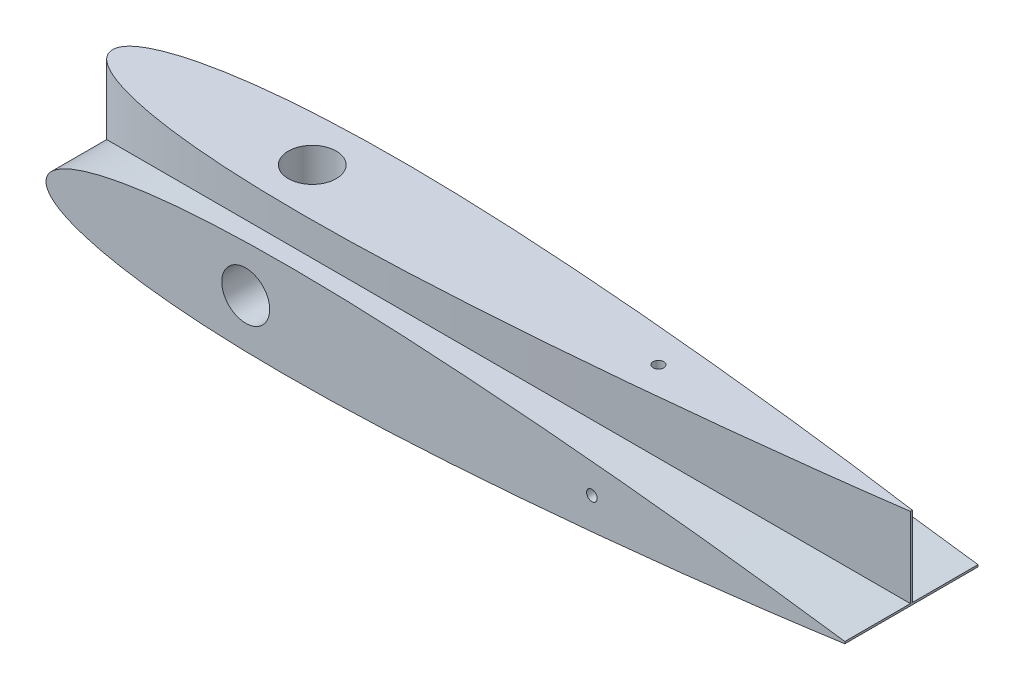
SolidWorks part; units mm, degrees
material "ABS"
ref_plane "Front Plane" through (0, 0, 0) normal (0, 0, 1) x (1, 0, 0)
ref_plane "Top Plane" through (0, 0, 0) normal (0, 1, 0) x (1, 0, 0)
ref_plane "Right Plane" through (0, 0, 0) normal (1, 0, 0) x (0, 0, -1)
sketch "Sketch5" plane through (0, 0, 0) normal (0, 0, 1) x (1, 0, 0)
  line L1 (300, 0) -> (300, -0.756)
  spline S1 degree 3 poles (300, 0) (299.2704, 0.1015) (297.2345, 0.3845) (293.6593, 0.8797) (289.1118, 1.4963) (284.0799, 2.1666) (278.7509, 2.8603) (273.2644, 3.5571) (267.7042, 4.2513) (262.1125, 4.9353) (256.5059, 5.6045) (250.889, 6.2603) (245.2665, 6.9042) (239.644, 7.5347) (234.0215, 8.1494) (228.3951, 8.7487) (222.764, 9.3356) (217.1313, 9.91) (211.5005, 10.4695) (205.8724, 11.0143) (200.246, 11.5435) (194.6206, 12.0573) (188.9966, 12.5546) (183.3751, 13.0358) (177.7564, 13.4991) (172.1412, 13.944) (166.5301, 14.3706) (160.924, 14.777) (155.3237, 15.1619) (149.7292, 15.5255) (144.14, 15.8647) (138.5567, 16.1803) (132.9816, 16.4703) (127.4179, 16.7331) (121.8677, 16.9668) (116.3306, 17.1682) (110.805, 17.3356) (105.2905, 17.4675) (99.7895, 17.5631) (94.306, 17.6196) (88.844, 17.6331) (83.4066, 17.6022) (77.9962, 17.5221) (72.6158, 17.39) (67.2698, 17.2024) (61.9642, 16.9545) (56.7072, 16.644) (51.5114, 16.2639) (46.3941, 15.8131) (41.3798, 15.2845) (36.501, 14.6768) (31.8041, 13.9884) (27.351, 13.2262) (23.2199, 12.4053) (19.4871, 11.5429) (16.2025, 10.6672) (13.3733, 9.7976) (10.9689, 8.956) (8.9454, 8.1445) (7.251, 7.3694) (5.8297, 6.633) (4.6313, 5.923) (3.6118, 5.2288) (2.7354, 4.5489) (1.9897, 3.8721) (1.374, 3.1924) (0.8844, 2.5131) (0.5127, 1.8423) (0.2438, 1.1885) (0.0691, 0.5531) (-0.0202, -0.069) (-0.0202, -0.687) (0.0691, -1.3091) (0.2438, -1.9446) (0.5127, -2.5984) (0.8844, -3.2691) (1.374, -3.9485) (1.9897, -4.6282) (2.7354, -5.3049) (3.6118, -5.9848) (4.6313, -6.679) (5.8297, -7.389) (7.251, -8.1254) (8.9454, -8.9006) (10.9689, -9.712) (13.3733, -10.5537) (16.2025, -11.4232) (19.4871, -12.2989) (23.2199, -13.1613) (27.351, -13.9824) (31.8042, -14.7439) (36.501, -15.433) (41.3798, -16.0405) (46.3941, -16.5691) (51.5114, -17.0199) (56.7072, -17.4) (61.9642, -17.7105) (67.2698, -17.9584) (72.6158, -18.146) (77.9962, -18.2782) (83.4066, -18.3583) (88.844, -18.3891) (94.306, -18.3756) (99.7895, -18.3191) (105.2905, -18.2235) (110.805, -18.0917) (116.3306, -17.9243) (121.8677, -17.7229) (127.4179, -17.4892) (132.9816, -17.2264) (138.5567, -16.9364) (144.14, -16.6208) (149.7292, -16.2816) (155.3237, -15.918) (160.924, -15.5331) (166.5301, -15.1267) (172.1412, -14.7001) (177.7564, -14.2552) (183.3751, -13.7919) (188.9966, -13.3107) (194.6206, -12.8133) (200.246, -12.2996) (205.8724, -11.7703) (211.5005, -11.2256) (217.1313, -10.6661) (222.764, -10.0916) (228.3951, -9.5048) (234.0215, -8.9055) (239.644, -8.2907) (245.2665, -7.6602) (250.889, -7.0164) (256.5059, -6.3605) (262.1125, -5.6914) (267.7042, -5.0073) (273.2644, -4.3132) (278.7509, -3.6163) (284.0799, -2.9227) (289.1118, -2.2524) (293.6593, -1.6358) (297.2345, -1.1406) (299.2704, -0.8575) (300, -0.756) knots 0 0 0 0 0.003612 0.010079 0.017699 0.026115 0.034971 0.04405 0.053234 0.062448 0.071674 0.080921 0.090178 0.099424 0.108664 0.117912 0.12717 0.136427 0.145675 0.154916 0.164153 0.173387 0.182616 0.191838 0.201053 0.21026 0.219459 0.228647 0.237822 0.246985 0.256137 0.265279 0.274407 0.283512 0.292592 0.301646 0.310682 0.319699 0.328695 0.33766 0.346589 0.355477 0.364323 0.373122 0.381868 0.390553 0.399166 0.40769 0.416098 0.424355 0.432412 0.440205 0.447631 0.454564 0.460855 0.466413 0.471229 0.475366 0.478901 0.481915 0.484499 0.486747 0.488741 0.490543 0.492182 0.493673 0.495032 0.496279 0.497425 0.49849 0.499503 0.500497 0.50151 0.502575 0.503721 0.504968 0.506327 0.507818 0.509457 0.511259 0.513253 0.515501 0.518085 0.521099 0.524634 0.528771 0.533587 0.539145 0.545436 0.55237 0.559795 0.567588 0.575645 0.583902 0.59231 0.600834 0.609447 0.618132 0.626878 0.635677 0.644523 0.653411 0.66234 0.671305 0.680301 0.689318 0.698354 0.707408 0.716488 0.725593 0.734721 0.743863 0.753015 0.762178 0.771353 0.780541 0.78974 0.798947 0.808162 0.817384 0.826613 0.835847 0.845084 0.854325 0.863573 0.87283 0.882088 0.891336 0.900576 0.909822 0.919079 0.928326 0.937552 0.946766 0.95595 0.965029 0.973885 0.982301 0.989921 0.996388 1 1 1 1
  dimension "Tail chord" = 300
extrude "Boss-Extrude1" add sketch "Sketch5" along normal blind 50
ref_plane "Plane1" through (0, 0, 60) normal (0, 0, 1) x (1, 0, 0)
curve "Curve6"
  spline degree 3 poles (298.242, -0.1932, 0) (300.4407, 0, 0) (298.242, 0.1932, 0) (296.4349, 0.5367, 0) (292.0253, 1.0976, 0) (286.5771, 1.8592, 0) (279.4156, 2.8001, 0) (270.9173, 3.8949, 0) (261.066, 5.1159, 0) (250.0071, 6.4339, 0) (237.8495, 7.8187, 0) (224.7304, 9.2395, 0) (210.7923, 10.6647, 0) (196.1883, 12.0613, 0) (181.0783, 13.3946, 0) (165.6277, 14.6278, 0) (150.0058, 15.7225, 0) (134.3834, 16.6392, 0) (118.9317, 17.3387, 0) (103.8195, 17.7845, 0) (89.2123, 17.9443, 0) (75.2698, 17.7935, 0) (62.1444, 17.3161, 0) (49.9793, 16.5075, 0) (38.907, 15.374, 0) (29.0471, 13.9333, 0) (20.5034, 12.2128, 0) (13.3641, 10.246, 0) (7.6828, 8.0707, 0) (3.4992, 5.7028, 0) (0.7348, 3.1014, 0) (-0.3264, 0, 0) (0.7348, -3.1014, 0) (3.4992, -5.7028, 0) (7.6828, -8.0707, 0) (13.3641, -10.246, 0) (20.5034, -12.2128, 0) (29.0471, -13.9333, 0) (38.907, -15.374, 0) (49.9793, -16.5075, 0) (62.1444, -17.3161, 0) (75.2698, -17.7935, 0) (89.2123, -17.9443, 0) (103.8195, -17.7845, 0) (118.9317, -17.3387, 0) (134.3834, -16.6392, 0) (150.0058, -15.7225, 0) (165.6277, -14.6278, 0) (181.0783, -13.3946, 0) (196.1883, -12.0613, 0) (210.7923, -10.6647, 0) (224.7304, -9.2395, 0) (237.8495, -7.8187, 0) (250.0071, -6.4339, 0) (261.066, -5.1159, 0) (270.9173, -3.8949, 0) (279.4156, -2.8001, 0) (286.5771, -1.8592, 0) (292.0253, -1.0976, 0) (296.4349, -0.5367, 0) (298.242, -0.1932, 0) (300.4407, 0, 0) (298.242, 0.1932, 0) knots -0.012119 -0.005412 -0.001357 0 0.001357 0.005412 0.012119 0.021403 0.033159 0.047255 0.063534 0.081814 0.101892 0.123547 0.146538 0.170613 0.195504 0.220938 0.246636 0.272314 0.297694 0.3225 0.346466 0.36934 0.390884 0.410879 0.429129 0.445462 0.459736 0.471848 0.481751 0.489494 0.495334 0.5 0.504666 0.510506 0.518249 0.528152 0.540264 0.554538 0.570871 0.589121 0.609116 0.63066 0.653534 0.6775 0.702306 0.727686 0.753364 0.779062 0.804496 0.829387 0.853462 0.876453 0.898108 0.918186 0.936466 0.952745 0.966841 0.978597 0.987881 0.994588 0.998643 1 1.001357 1.005412 1.012119 periodic
sketch "Sketch10" plane through (0, 0, 0) normal (0, 1, 0) x (1, 0, 0)
  line L0 (300, 0) -> (0, 0) construction
  line L1 (300, -24.622) -> (300, -25.378)
  line L2 (300, -50) -> (300, 0) construction
  line L3 (300, -25) -> (300.5696, -25) construction
  line L5 (0, -77.0538) -> (0, 20.1337) construction
  line L6 (300, -66.8262) -> (300, 15.682) construction
  line L7 (-23.0118, -25) -> (350.8298, -25) construction
  spline S1 degree 3 poles (300, -24.622) (299.2704, -24.5206) (297.2347, -24.2375) (293.6596, -23.7423) (289.1124, -23.1258) (284.0808, -22.4555) (278.752, -21.7619) (273.2659, -21.0651) (267.7059, -20.371) (262.1146, -19.6869) (256.5083, -19.0178) (250.8917, -18.362) (245.2695, -17.7182) (239.6473, -17.0878) (234.0251, -16.473) (228.3991, -15.8738) (222.7682, -15.2869) (217.1359, -14.7125) (211.5054, -14.1531) (205.8776, -13.6084) (200.2515, -13.0791) (194.6264, -12.5654) (189.0028, -12.0681) (183.3815, -11.5869) (177.7632, -11.1236) (172.1483, -10.6788) (166.5375, -10.2522) (160.9317, -9.8458) (155.3317, -9.4609) (149.7375, -9.0973) (144.1487, -8.7582) (138.5656, -8.4426) (132.9908, -8.1526) (127.4274, -7.8898) (121.8776, -7.6561) (116.3407, -7.4547) (110.8154, -7.2873) (105.3012, -7.1555) (99.8005, -7.0599) (94.3174, -7.0034) (88.8557, -6.9899) (83.4186, -7.0208) (78.0084, -7.1008) (72.6284, -7.233) (67.2827, -7.4206) (61.9773, -7.6685) (56.7206, -7.979) (51.5251, -8.359) (46.4081, -8.8098) (41.3941, -9.3383) (36.5156, -9.946) (31.8189, -10.6344) (27.3661, -11.3965) (23.2352, -12.2174) (19.5026, -13.0797) (16.2182, -13.9554) (13.3891, -14.8249) (10.9849, -15.6665) (8.9615, -16.4779) (7.2672, -17.253) (5.846, -17.9894) (4.6476, -18.6994) (3.6282, -19.3935) (2.7518, -20.0734) (2.0062, -20.7501) (1.3905, -21.4297) (0.9009, -22.1091) (0.5292, -22.7798) (0.2604, -23.4335) (0.0856, -24.069) (-0.0036, -24.691) (-0.0036, -25.309) (0.0856, -25.931) (0.2604, -26.5665) (0.5292, -27.2202) (0.9009, -27.8909) (1.3905, -28.5703) (2.0062, -29.2499) (2.7518, -29.9266) (3.6282, -30.6065) (4.6476, -31.3006) (5.846, -32.0106) (7.2672, -32.747) (8.9615, -33.5221) (10.9849, -34.3335) (13.3891, -35.1751) (16.2182, -36.0446) (19.5026, -36.9203) (23.2352, -37.7826) (27.3661, -38.6036) (31.819, -39.3651) (36.5156, -40.0541) (41.3941, -40.6616) (46.4081, -41.1902) (51.5251, -41.641) (56.7206, -42.021) (61.9773, -42.3315) (67.2827, -42.5794) (72.6284, -42.767) (78.0084, -42.8992) (83.4186, -42.9792) (88.8557, -43.0101) (94.3174, -42.9966) (99.8005, -42.9401) (105.3012, -42.8445) (110.8154, -42.7127) (116.3407, -42.5453) (121.8776, -42.3439) (127.4274, -42.1102) (132.9908, -41.8474) (138.5656, -41.5574) (144.1487, -41.2418) (149.7375, -40.9027) (155.3317, -40.5391) (160.9317, -40.1542) (166.5375, -39.7478) (172.1483, -39.3212) (177.7632, -38.8764) (183.3815, -38.4131) (189.0028, -37.9319) (194.6264, -37.4346) (200.2515, -36.9209) (205.8776, -36.3916) (211.5054, -35.8469) (217.1359, -35.2875) (222.7682, -34.7131) (228.3991, -34.1262) (234.0251, -33.527) (239.6473, -32.9122) (245.2695, -32.2818) (250.8917, -31.638) (256.5083, -30.9822) (262.1146, -30.3131) (267.7059, -29.629) (273.2659, -28.9349) (278.752, -28.2381) (284.0808, -27.5445) (289.1124, -26.8742) (293.6596, -26.2577) (297.2347, -25.7625) (299.2704, -25.4794) (300, -25.378) knots 0 0 0 0 0.003612 0.010079 0.017699 0.026115 0.034971 0.04405 0.053234 0.062448 0.071674 0.080921 0.090178 0.099424 0.108664 0.117912 0.12717 0.136427 0.145675 0.154916 0.164153 0.173387 0.182616 0.191838 0.201053 0.21026 0.219459 0.228647 0.237822 0.246985 0.256137 0.265279 0.274407 0.283512 0.292592 0.301646 0.310682 0.319699 0.328695 0.33766 0.346589 0.355477 0.364323 0.373122 0.381868 0.390553 0.399166 0.40769 0.416098 0.424355 0.432412 0.440205 0.447631 0.454564 0.460855 0.466413 0.471229 0.475366 0.478901 0.481915 0.484499 0.486747 0.488741 0.490543 0.492182 0.493673 0.495032 0.496279 0.497425 0.49849 0.499503 0.500497 0.50151 0.502575 0.503721 0.504968 0.506327 0.507818 0.509457 0.511259 0.513253 0.515501 0.518085 0.521099 0.524634 0.528771 0.533587 0.539145 0.545436 0.55237 0.559795 0.567588 0.575645 0.583902 0.59231 0.600834 0.609447 0.618132 0.626878 0.635677 0.644523 0.653411 0.66234 0.671305 0.680301 0.689318 0.698354 0.707408 0.716488 0.725593 0.734721 0.743863 0.753015 0.762178 0.771353 0.780541 0.78974 0.798947 0.808162 0.817384 0.826613 0.835847 0.845084 0.854325 0.863573 0.87283 0.882088 0.891336 0.900576 0.909822 0.919079 0.928326 0.937552 0.946766 0.95595 0.965029 0.973885 0.982301 0.989921 0.996388 1 1 1 1
  dimension "D1" = 25
extrude "Boss-Extrude2" add sketch "Sketch10" along normal blind 30
ref_plane "Plane3" through (0, 30, 0) normal (0, 1, 0) x (1, 0, 0)
sketch "Sketch13" plane through (0, 30, 0) normal (0, 1, 0) x (1, 0, 0)
  line L0 (-23.0118, -25) -> (350.8298, -25) construction
  line L1 (-0.0166, 0) -> (-0.0166, -50) construction
  circle A0 centre (74.9834, -25) radius 9
  circle A1 centre (204.9834, -25) radius 2
  dimension "D1" = 18
  dimension "D2" = 4
  dimension "Small hole post" = 130
  dimension "Tail chord qtr" = 75
  dimension "D3" = 0
  dimension "D4" = 0
extrude "Cut-Extrude8" cut sketch "Sketch13" against normal blind 20
sketch "Sketch7" plane through (0, 0, 60) normal (0, 0, 1) x (1, 0, 0)
  circle A0 centre (75, 0) radius 9
  circle A1 centre (205, 0) radius 2
  dimension "D1" = 18
  dimension "D3" = 4
  dimension "Tail chord qtr vert" = 75
  dimension "Small hole" = 130
extrude "Cut-Extrude7" cut sketch "Sketch7" against normal through all
equation "\"Tail chord qtr@Sketch13\" = \"Tail chord@Sketch5\" * 0.25"
equation "\"Tail chord qtr vert@Sketch7\" = \"Tail chord qtr@Sketch13\""
equation "\"Small hole@Sketch7\" = \"Tail chord qtr@Sketch13\" * 2 - 20"
equation "\"Small hole post@Sketch13\" = \"Tail chord qtr@Sketch13\" * 2 - 20"
equation "\"Chord\"= 300mm'Tail chord"
equation "\"Tail chord@Sketch5\"=\"Chord\""
